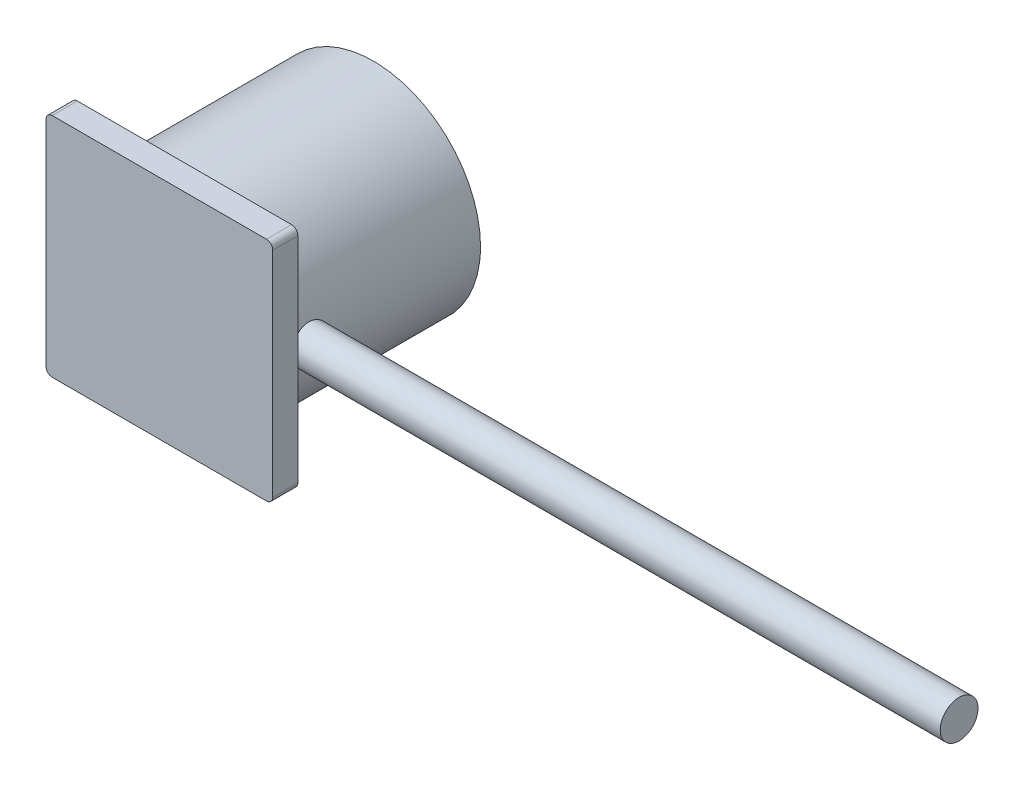
SolidWorks part; units mm, degrees
ref_plane "Plan de face" through (0, 0, 0) normal (0, 0, 1) x (1, 0, 0)
ref_plane "Plan de dessus" through (0, 0, 0) normal (0, 1, 0) x (1, 0, 0)
ref_plane "Plan de droite" through (0, 0, 0) normal (1, 0, 0) x (0, 0, -1)
sketch "Esquisse1" plane through (0, 0, 0) normal (0, 0, 1) x (1, 0, 0)
  circle A0 centre (0, 0) radius 85
  dimension "D1" = 170
extrude "Boss.-Extru.1" add sketch "Esquisse1" along normal blind 150
sketch "Esquisse2" plane through (0, 0, 150) normal (0, 0, 1) x (1, 0, 0)
  line L0 (-110.1154, 0) -> (117.3282, 0) construction
  line L1 (-90, 90) -> (90, 90)
  line L2 (-90, 90) -> (-90, -90)
  line L3 (-90, -90) -> (90, -90)
  line L4 (90, 90) -> (90, -90)
  line L5 (0, 101.9602) -> (0, -123.0793) construction
  dimension "D1" = 180
  dimension "D2" = 180
extrude "Boss.-Extru.2" add sketch "Esquisse2" along normal blind 20
fillet "Congé1" radius 5 1 edges at (85, 0, 150)
fillet "Congé2" radius 5 1 edges at (-90, 90, 160)
fillet "Congé3" radius 5 1 edges at (-90, -90, 160)
fillet "Congé4" radius 5 1 edges at (90, 90, 160)
fillet "Congé5" radius 5 1 edges at (90, -90, 160)
sketch "Esquisse3" plane through (0, 0, 0) normal (0, 0, -1) x (-1, 0, 0)
  line L0 (0, 0) -> (0, 180.7973)
curve "Courbe1"
  spline degree 1 poles (100, 0, 135) (500, 0, 135) knots 0 0 1 1
sketch "Esquisse4" plane through (0, 0, 0) normal (1, 0, 0) x (0, 0, -1)
  line L0 (0, -85) -> (0, 85) construction
  circle A0 centre (-135, 0) radius 15
  point P2 (0, 0)
  point P3 (0, 0)
  point P4 (0, 0)
  dimension "D2" = 30
  dimension "D1" = 135
extrude "Boss.-Extru.3" add sketch "Esquisse4" along normal blind 600
